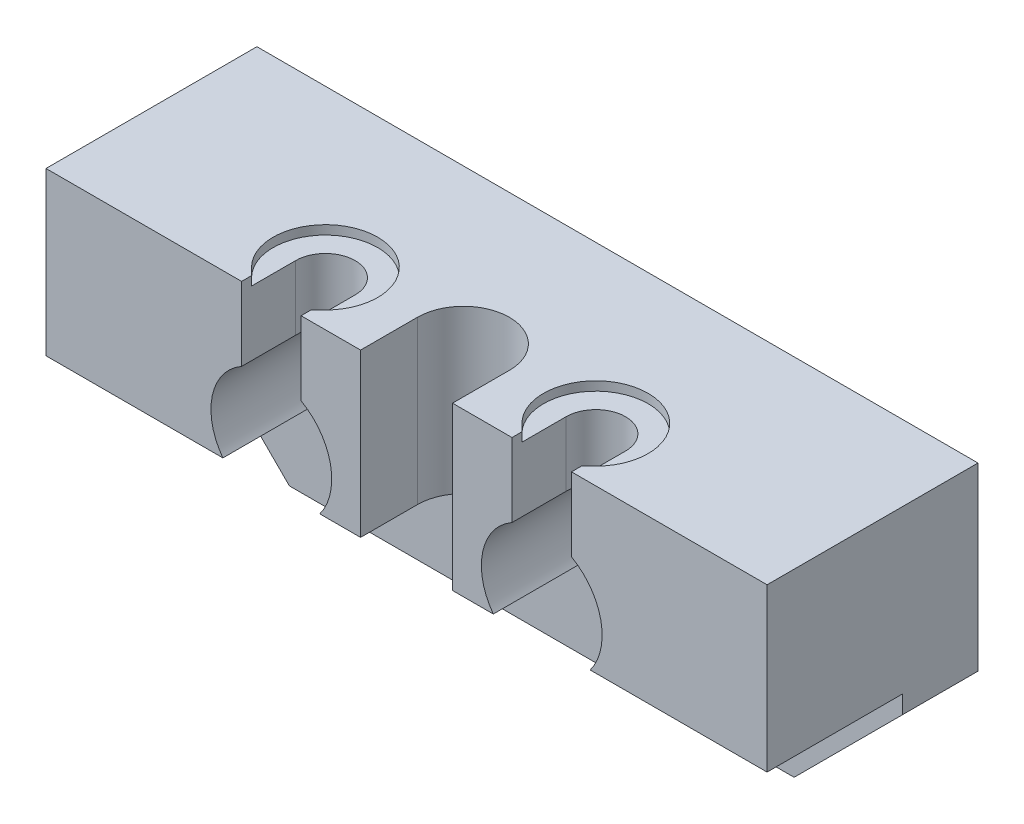
SolidWorks part; units mm, degrees
ref_plane "Front Plane" through (0, 0, 0) normal (0, 0, 1) x (1, 0, 0)
ref_plane "Top Plane" through (0, 0, 0) normal (0, 1, 0) x (1, 0, 0)
ref_plane "Right Plane" through (0, 0, 0) normal (1, 0, 0) x (0, 0, -1)
sketch "Sketch1" plane through (0, 0, 0) normal (0, 0, 1) x (1, 0, 0)
  line L1 (-20, 0) -> (20, 0)
  line L2 (-20, 0) -> (-20, 16)
  line L3 (-20, 16) -> (20, 16)
  line L4 (20, 0) -> (20, 16)
  dimension "D2" = 40
  dimension "D3" = 16
extrude "Boss-Extrude1" add sketch "Sketch1" along normal blind 12
sketch "Sketch2" plane through (0, 0, 12) normal (0, 0, 1) x (1, 0, 0)
  line L0 (0, 8) -> (0, 9) construction
  line L2 (-7.5, 9) -> (7.5, 9) construction
  line L3 (20, 16) -> (-20, 16) construction
  line L4 (-7.5, 5) -> (-7.5, 13) construction
  line L5 (-9.15, 5) -> (-9.15, 13) construction
  line L6 (-5.85, 5) -> (-5.85, 13) construction
  line L7 (7.5, 5) -> (7.5, 13) construction
  line L8 (5.85, 5) -> (5.85, 13) construction
  line L9 (9.15, 5) -> (9.15, 13) construction
  line L10 (-16, 8) -> (16, 8) construction
  arc A0 (-9.15, 5) -> (-5.85, 5) centre (-7.5, 5) ccw construction
  arc A1 (-5.85, 13) -> (-9.15, 13) centre (-7.5, 13) ccw construction
  arc A2 (5.85, 5) -> (9.15, 5) centre (7.5, 5) ccw construction
  arc A3 (9.15, 13) -> (5.85, 13) centre (7.5, 13) ccw construction
  circle A4 centre (-16, 8) radius 1.7784 construction
  circle A5 centre (16, 8) radius 1.7784 construction
  circle A6 centre (-7.5, 9) radius 1.65
  circle A7 centre (7.5, 9) radius 1.65
  point P8 (-7.5, 9)
  point P15 (7.5, 9)
  dimension "D1" = 1.65
  dimension "D2" = 8
  dimension "D3" = 7
  dimension "D4" = 15
  dimension "D5" = 1
  dimension "D6" = 32
extrude "Cut-Extrude1" cut sketch "Sketch2" against normal through all
sketch "Sketch5" plane through (0, 16, 0) normal (0, 1, 0) x (1, 0, 0)
  line L0 (0, 0) -> (0, -9) construction
  line L1 (-7.5, -9) -> (7.5, -9) construction
  line L2 (20, -12) -> (-20, -12) construction
  line L3 (-9.15, -9) -> (-9.15, -12)
  line L4 (-9.15, -12) -> (-5.85, -12)
  line L5 (-5.85, -12) -> (-5.85, -9)
  line L6 (5.85, -9) -> (5.85, -12)
  line L7 (5.85, -12) -> (9.15, -12)
  line L8 (9.15, -12) -> (9.15, -9)
  arc A0 (-5.85, -9) -> (-9.15, -9) centre (-7.5, -9) ccw
  arc A1 (9.15, -9) -> (5.85, -9) centre (7.5, -9) ccw
  dimension "D2" = 3.3
  dimension "D1" = 15
  dimension "D3" = 3
extrude "Cut-Extrude4" cut sketch "Sketch5" against normal through all
ref_axis "Axis1" through (7.5, 9, 9) along (0, 1, 0)
sketch "Sketch6" plane through (20, 0, 0) normal (1, 0, 0) x (0, 0, -1)
  line L0 (-12, 7) -> (-4.5, 7)
  line L3 (-4.5, 7) -> (-4.5, 0)
  line L4 (-12, 0) -> (0, 0) construction
  line L5 (-4.5, 0) -> (-12, 0)
  line L6 (-12, 0) -> (-12, 7)
  line L8 (-12, 16) -> (0, 16) construction
  line L9 (0, 0) -> (0, 16) construction
  dimension "D1" = 9
  dimension "D2" = 4.5
extrude "Cut-Extrude5" cut sketch "Sketch6" against normal through all
sketch "Sketch7" plane through (0, 16, 0) normal (0, 1, 0) x (1, 0, 0)
  line L1 (-9.5506, -11.0506) -> (-7.5, -13.1012)
  line L2 (-7.5, -13.1012) -> (-5.4494, -11.0506)
  line L3 (0, 0) -> (0, -12) construction
  line L4 (20, 0) -> (-20, 0) construction
  line L6 (7.5, -13.1012) -> (5.4494, -11.0506)
  line L7 (9.5506, -11.0506) -> (7.5, -13.1012)
  arc A0 (-5.4494, -11.0506) -> (-9.5506, -11.0506) centre (-7.5, -9) ccw
  arc A1 (5.4494, -11.0506) -> (9.5506, -11.0506) centre (7.5, -9) cw
  dimension "D1" = 5.8
extrude "Cut-Extrude6" cut sketch "Sketch7" against normal blind 0.5
chamfer "Chamfer4" [suppressed] distance 1.8 angle 45
sketch "Sketch8" plane through (0, 16, 0) normal (0, 1, 0) x (1, 0, 0)
  line L0 (-2.55, -8.8461) -> (-2.55, -12)
  line L1 (6.3988, -12) -> (-6.3988, -12) construction
  line L2 (-2.55, -12) -> (2.55, -12)
  line L3 (2.55, -12) -> (2.55, -8.8461)
  arc A0 (2.55, -9.0461) -> (-2.55, -9.0461) centre (0, -9.0461) ccw construction
  arc A1 (2.55, -8.8461) -> (-2.55, -8.8461) centre (0, -8.8461) ccw
  dimension "D1" = 2.55
  dimension "D2" = 0.2
extrude "Cut-Extrude7" cut sketch "Sketch8" against normal through all
sketch "Sketch9" plane through (0, 0, 12) normal (0, 0, 1) x (1, 0, 0)
  circle A0 centre (-7.5, 9) radius 3.35
  circle A1 centre (7.5, 9) radius 3.35
  dimension "D1" = 6.7
extrude "Cut-Extrude8" cut sketch "Sketch9" against normal up to surface (7.5 mm away) up to face at (0, 3.5, 4.5)
chamfer "Chamfer5" distance 1.8 angle 45 2 edges at (-7.5, 10.65, 4.5) (7.5, 10.65, 4.5)
chamfer "Chamfer6" distance 6 angle 45 2 edges at (20, 0, 2.25) (-20, 0, 2.25)
chamfer "Chamfer7" distance 0.3 angle 45 8 edges at (0, 16, 0) (-20, 11, 0) (-17, 3, 0) (0, 0, 0) (17, 3, 0) (20, 11, 0) (-5.85, 9, 0) (9.15, 9, 0)
sketch "Sketch10" plane through (0, 15.5, 0) normal (0, 1, 0) x (1, 0, 0)
  circle A0 centre (7.5, -9) radius 2.9
  circle A1 centre (-7.5, -9) radius 2.9
  arc A4 (-5.4494, -11.0506) -> (-9.5506, -11.0506) centre (-7.5, -9) ccw construction
  arc A5 (9.5506, -11.0506) -> (5.4494, -11.0506) centre (7.5, -9) ccw construction
  dimension "D1" = 5.8
extrude "Cut-Extrude9" [suppressed] cut sketch "Sketch10" against normal blind 0.5
equation "\"y-cross-rib-thickness\"=6"
equation "\"y-rib-thickness\"=6"
equation "\"bed-plate-thickness\"=6"
equation "\"x-plate-thickness\"=5"
equation "\"rod-diameter\"=12"
equation "\"t-nut-hole-diameter\"=3"
equation "\"y-plate-thickness\"=5"
equation "\"enclosure-thickness\"=0.6"
equation "\"M3-Clearance\"=3.3"
equation "\"M4-Clearance\"=4.3"
equation "\"M5-Clearance\"=5.3"
equation "\"M6-Clearance\"=6.3"
equation "\"M8-Clearance\"=8.3"
equation "\"623-Bearing-Dia\"=11.2"
